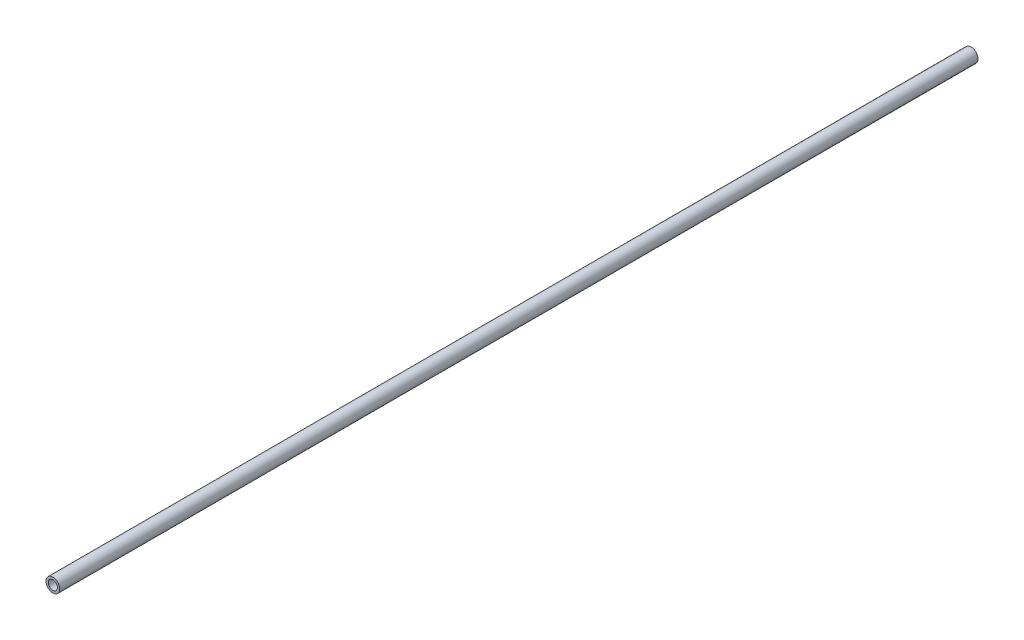
SolidWorks part; units mm, degrees
ref_plane "Front Plane" through (0, 0, 0) normal (0, 0, 1) x (1, 0, 0)
ref_plane "Top Plane" through (0, 0, 0) normal (0, 1, 0) x (1, 0, 0)
ref_plane "Right Plane" through (0, 0, 0) normal (1, 0, 0) x (0, 0, -1)
sketch "Sketch1" plane through (0, 0, 0) normal (0, 0, 1) x (1, 0, 0)
  circle A0 centre (0, 0) radius 3
  circle A1 centre (0, 0) radius 2
  dimension "D1" = 6
  dimension "D2" = 4
extrude "Boss-Extrude1" add sketch "Sketch1" along normal blind 400
